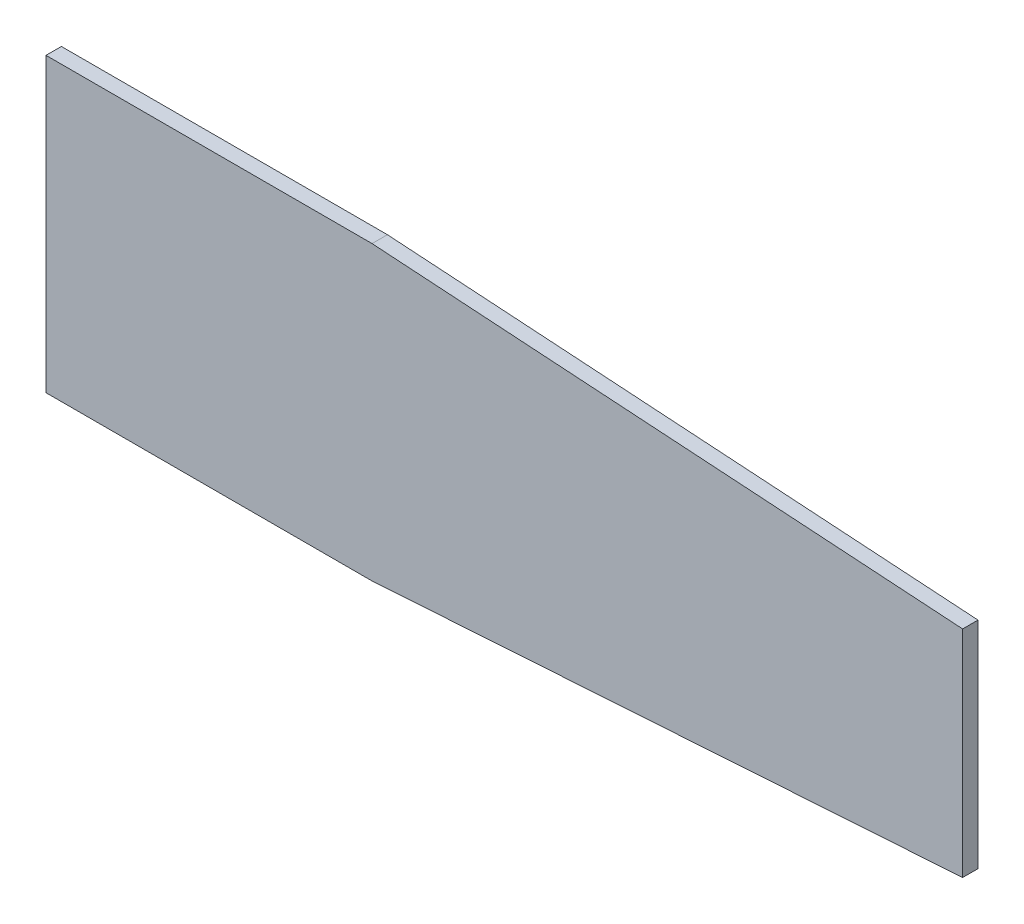
SolidWorks part; units mm, degrees
ref_plane "Ebene vorne" through (0, 0, 0) normal (0, 0, 1) x (1, 0, 0)
ref_plane "Ebene oben" through (0, 0, 0) normal (0, 1, 0) x (1, 0, 0)
ref_plane "Ebene rechts" through (0, 0, 0) normal (1, 0, 0) x (0, 0, -1)
sketch "Skizze1" plane through (0, 0, 0) normal (0, 0, 1) x (1, 0, 0)
  line L0 (0, 0) -> (298, 0) construction
  line L1 (0, -47.5) -> (0, 47.5)
  line L2 (0, 47.5) -> (106, 47.5)
  line L3 (106, 47.5) -> (298, 35)
  line L4 (298, 35) -> (298, -35)
  line L5 (106, -47.5) -> (298, -35)
  line L6 (0, -47.5) -> (106, -47.5)
  dimension "D1" = 95
  dimension "D2" = 298
  dimension "D3" = 70
  dimension "D4" = 192
extrude "Grundplatte" add sketch "Skizze1" along normal blind 5
